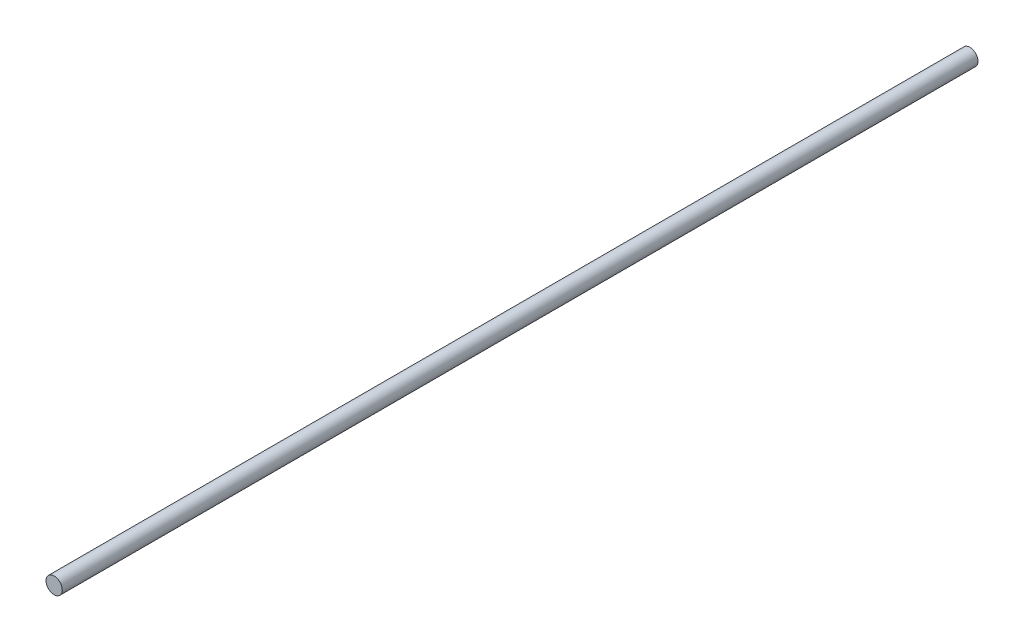
SolidWorks part; units mm, degrees
ref_plane "Front Plane" through (0, 0, 0) normal (0, 0, 1) x (1, 0, 0)
ref_plane "Top Plane" through (0, 0, 0) normal (0, 1, 0) x (1, 0, 0)
ref_plane "Right Plane" through (0, 0, 0) normal (1, 0, 0) x (0, 0, -1)
sketch "Sketch1" plane through (0, 0, 0) normal (0, 0, 1) x (1, 0, 0)
  circle A0 centre (0, 0) radius 4
  dimension "D1" = 8
extrude "Boss-Extrude1" add sketch "Sketch1" against normal blind 450
sketch "Sketch2" plane through (0, 0, 0) normal (0, 0, 1) x (1, 0, 0)
  circle A0 centre (0, 0) radius 4
  dimension "D1" = 8
curve "Helix/Spiral1" pitch 2 height 400 turns 200
sketch "Croquis1" plane through (0, 0, -450) normal (0, 0, -1) x (-1, 0, 0)
  line L1 (3, 6.4049) -> (5, 6.4049)
  line L2 (3, 6.4049) -> (3, -5.5951)
  line L3 (3, -5.5951) -> (5, -5.5951)
  line L4 (5, 6.4049) -> (5, -5.5951)
  dimension "D1" = 12
  dimension "D2" = 2
  dimension "D3" = 3
extrude "Cortar-Extruir1" cut sketch "Croquis1" against normal blind 10
